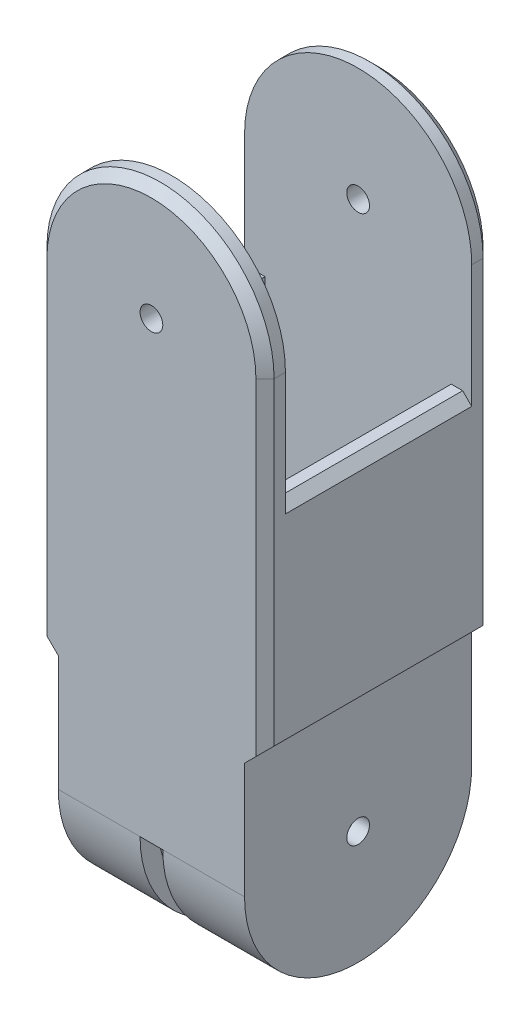
SolidWorks part; units mm, degrees
ref_plane "Front Plane" through (0, 0, 0) normal (0, 0, 1) x (1, 0, 0)
ref_plane "Top Plane" through (0, 0, 0) normal (0, 1, 0) x (1, 0, 0)
ref_plane "Right Plane" through (0, 0, 0) normal (1, 0, 0) x (0, 0, -1)
sketch "Sketch1" plane through (0, 0, 0) normal (0, 1, 0) x (1, 0, 0)
  line L1 (-25, -25) -> (25, -25)
  line L2 (-25, -25) -> (-25, 25)
  line L3 (-25, 25) -> (25, 25)
  line L4 (25, -25) -> (25, 25)
  line L5 (-25, -25) -> (25, 25) construction
  line L6 (-25, 25) -> (25, -25) construction
  point P0 (0, 0)
  dimension "D1" = 50
  dimension "D2" = 50
extrude "Boss-Extrude1" add sketch "Sketch1" along normal blind 100
sketch "Sketch4" plane through (0, 0, -25) normal (0, 0, -1) x (-1, 0, 0)
  line L0 (25, 100) -> (25, 0) construction
  line L1 (-25, 100) -> (25, 100)
  line L2 (-25, 100) -> (-25, 125)
  line L4 (25, 100) -> (25, 125)
  arc A0 (-25, 125) -> (25, 125) centre (0, 125) cw
  circle A1 centre (0, 125) radius 2.5
  dimension "D2" = 5
  dimension "D1" = 25
extrude "Boss-Extrude2" add sketch "Sketch4" against normal blind 4.5
mirror "Mirror2" about plane through (0, 0, 0) normal (0, 0, 1) of "Boss-Extrude2"
sketch "Sketch5" plane through (25, 0, 0) normal (-1, 0, 0) x (0, 0, 1)
  line L0 (0, -27.5) -> (0, 27.5) construction
  line L1 (27.5, 0) -> (-27.5, 0) construction
  line L2 (-25, 125) -> (-25, 0) construction
  line L3 (25, 25) -> (25, 0)
  line L4 (25, 0) -> (-25, 0)
  line L5 (-25, 0) -> (-25, 25)
  arc A0 (-25, 25) -> (25, 25) centre (0, 25) ccw
  circle A1 centre (0, 25) radius 2.5
  point P15 (0, 0)
  line M6 (25, 0) -> (-25, 0)
  line M7 (-25, 0) -> (-25, 125)
  line M13 (25, 125) -> (25, 0)
  dimension "D1" = 5
extrude "Cut-Extrude1" cut sketch "Sketch5" along normal through all both and the other way through all contours A0 L4 M7 | A0 M6 M13 | A1 region at (25, 5.5842, -19.4158) region at (25, 5.5842, 19.4158)
sketch "Sketch6" plane through (25, 0, 0) normal (1, 0, 0) x (0, 0, -1)
  line L0 (-25, 50) -> (25, 50)
  line L1 (-25, 125) -> (-25, 25) construction
  line L2 (25, 125) -> (25, 25) construction
  line L3 (25, 50) -> (25, 0)
  line L4 (27.5, 0) -> (-27.5, 0) construction
  line L5 (25, 0) -> (-25, 0)
  line L6 (-25, 0) -> (-25, 50)
  circle A0 centre (0, 25) radius 25 construction
extrude "Cut-Extrude2" cut sketch "Sketch6" against normal blind 4.5
mirror "Mirror3" about plane through (0, 0, 0) normal (1, 0, 0) of "Cut-Extrude2"
chamfer "Chamfer1" distance 2 angle 45 8 edges at (-25, 100, 0) (25, 100, 0) (-25, 87.5, -25) (25, 87.5, -25) (0, 150, -25) (-25, 87.5, 25) (25, 87.5, 25) (0, 150, 25)
chamfer "Chamfer2" distance 5 angle 45 2 edges at (25, 50, 0) (-25, 50, 0)
sketch "Sketch7" plane through (0, 100, 0) normal (0, 1, 0) x (1, 0, 0)
  line L0 (-25, 20.5) -> (25, 20.5) construction
  line L1 (-20.5, -20.5) -> (20.5, -20.5)
  line L2 (-20.5, -20.5) -> (-20.5, 20.5)
  line L3 (-20.5, 20.5) -> (20.5, 20.5)
  line L4 (20.5, -20.5) -> (20.5, 20.5)
  line L5 (-20.5, -20.5) -> (20.5, 20.5) construction
  line L6 (-20.5, 20.5) -> (20.5, -20.5) construction
  line L7 (25, 20.5) -> (25, -20.5) construction
  point P0 (0, 0)
  dimension "D1" = 4.5
extrude "Cut-Extrude3" cut sketch "Sketch7" against normal up to vertex (45 mm away) up to point (25, 55, 23)
sketch "Sketch8" plane through (0, 55, 0) normal (0, 1, 0) x (1, 0, 0)
  line L0 (-25, 20.5) -> (25, 20.5) construction
  line L1 (-17, -20.5) -> (17, -20.5)
  line L2 (-17, -20.5) -> (-17, 20.5)
  line L3 (-17, 20.5) -> (17, 20.5)
  line L4 (17, -20.5) -> (17, 20.5)
  line L5 (-17, -20.5) -> (17, 20.5) construction
  line L6 (-17, 20.5) -> (17, -20.5) construction
  line L7 (25, 20.5) -> (25, -20.5) construction
  point P0 (0, 0)
  dimension "D1" = 8
extrude "Cut-Extrude4" cut sketch "Sketch8" against normal up to vertex (30 mm away) up to point (20.5, 25, 25)
sketch "Sketch9" plane through (17, 0, 0) normal (-1, 0, 0) x (0, 0, 1)
  line L0 (0, -27.5) -> (0, 27.5) construction
  line L1 (-21, 25) -> (21, 25)
  arc A0 (21, 25) -> (-21, 25) centre (0, 25) cw
  dimension "D1" = 4
  dimension "D2" = 4
extrude "Cut-Extrude5" cut sketch "Sketch9" along normal up to surface (34 mm away) up to face at (-17, 35.4167, 0)
sketch "Sketch10" plane through (0, 0, 0) normal (0, 1, 0) x (1, 0, 0)
  line L1 (2.5, 25.1331) -> (-2.5, 25.1331)
  line L2 (2.5, 25.1331) -> (2.5, -25.1331)
  line L3 (2.5, -25.1331) -> (-2.5, -25.1331)
  line L4 (-2.5, 25.1331) -> (-2.5, -25.1331)
  line L5 (2.5, 25.1331) -> (-2.5, -25.1331) construction
  line L6 (2.5, -25.1331) -> (-2.5, 25.1331) construction
  point P0 (0, 0)
  dimension "D1" = 5
extrude "Cut-Extrude6" cut sketch "Sketch10" along normal up to vertex (25 mm away) up to point (20.5, 25, 25)
